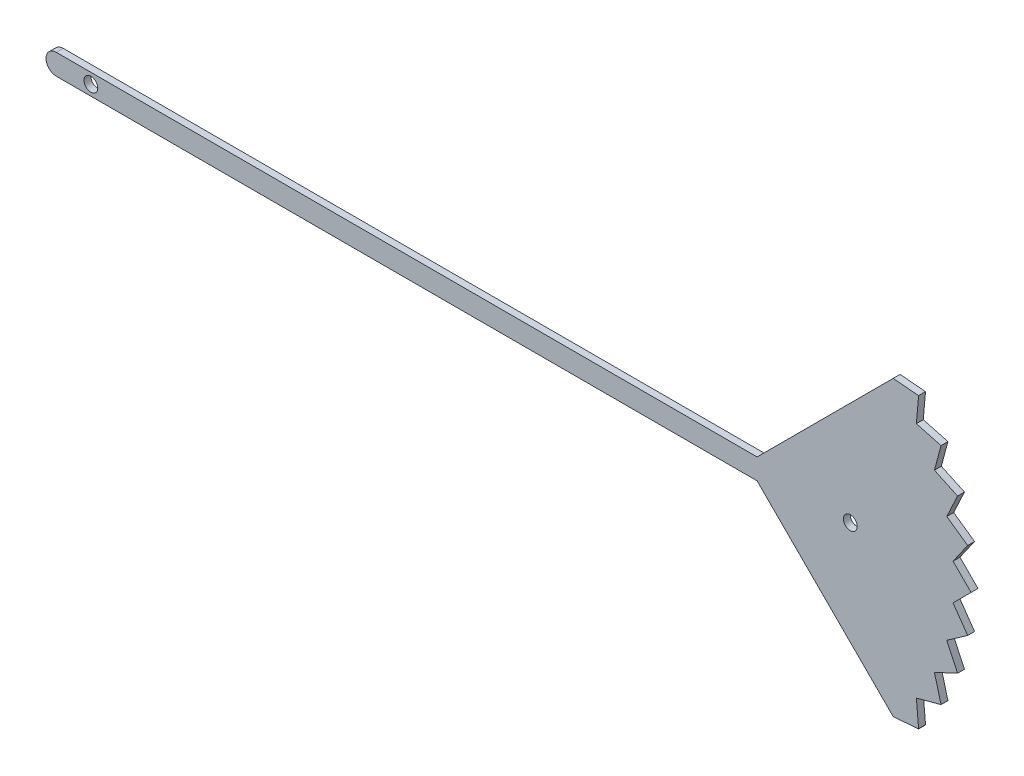
SolidWorks part; units mm, degrees
ref_plane "前视基准面" through (0, 0, 0) normal (0, 0, 1) x (1, 0, 0)
ref_plane "上视基准面" through (0, 0, 0) normal (0, 1, 0) x (1, 0, 0)
ref_plane "右视基准面" through (0, 0, 0) normal (1, 0, 0) x (0, 0, -1)
sketch "草图1" plane through (0, 0, 0) normal (0, 0, 1) x (1, 0, 0)
  line L1 (-62.7324, -3) -> (140.2879, -3)
  line L2 (-62.7324, 3) -> (140.2879, 3)
  line L3 (140.2879, 3) -> (179.7143, 42.4264)
  line L4 (140.2879, -3) -> (179.7143, -42.4264)
  line L25 (179.7143, 42.4264) -> (187.0808, 41.7812)
  line L26 (186.4371, 34.4146) -> (187.0808, 41.7812)
  line L27 (193.5796, 32.5) -> (186.4371, 34.4146)
  line L28 (193.5796, 32.5) -> (191.6664, 25.3571)
  line L29 (198.368, 22.2313) -> (191.6664, 25.3571)
  line L30 (198.368, 22.2313) -> (195.2435, 15.5291)
  line L31 (195.2435, 15.5291) -> (201.3004, 11.2871)
  line L32 (201.3004, 11.2871) -> (197.0596, 5.2293)
  line L33 (197.0596, 5.2293) -> (202.2879, 0)
  line L34 (202.2879, 0) -> (197.0596, -5.2293)
  line L35 (197.0596, -5.2293) -> (201.3004, -11.2871)
  line L36 (195.2435, -15.5291) -> (201.3004, -11.2871)
  line L37 (195.2435, -15.5291) -> (198.368, -22.2313)
  line L38 (198.368, -22.2313) -> (191.6664, -25.3571)
  line L39 (193.5796, -32.5) -> (191.6664, -25.3571)
  line L40 (193.5796, -32.5) -> (186.4371, -34.4146)
  line L41 (186.4371, -34.4146) -> (187.0808, -41.7812)
  line L42 (187.0808, -41.7812) -> (187.0587, -41.8804)
  line L43 (187.0587, -41.8804) -> (179.7143, -42.4264)
  arc A0 (-62.6918, 3) -> (-62.6918, -3) centre (-62.7121, 0) ccw
  circle A1 centre (-52.7121, 0) radius 2
  circle A2 centre (167.2879, 0) radius 2
  dimension "D1" = 10
extrude "凸台-拉伸1" add sketch "草图1" along normal mid plane 2 contours L2 A0 L1 L4 L43 L42 L41 L40 L39 L38 L37 L36 L35 L34 L33 L32 L31 L30 L29 L28 L27 L26 L25 L3 A2 region at (135.8519, -0.0035, 0)
ref_axis "基准轴1" through (-52.7121, 0, 1) along (0, 0, -1)
